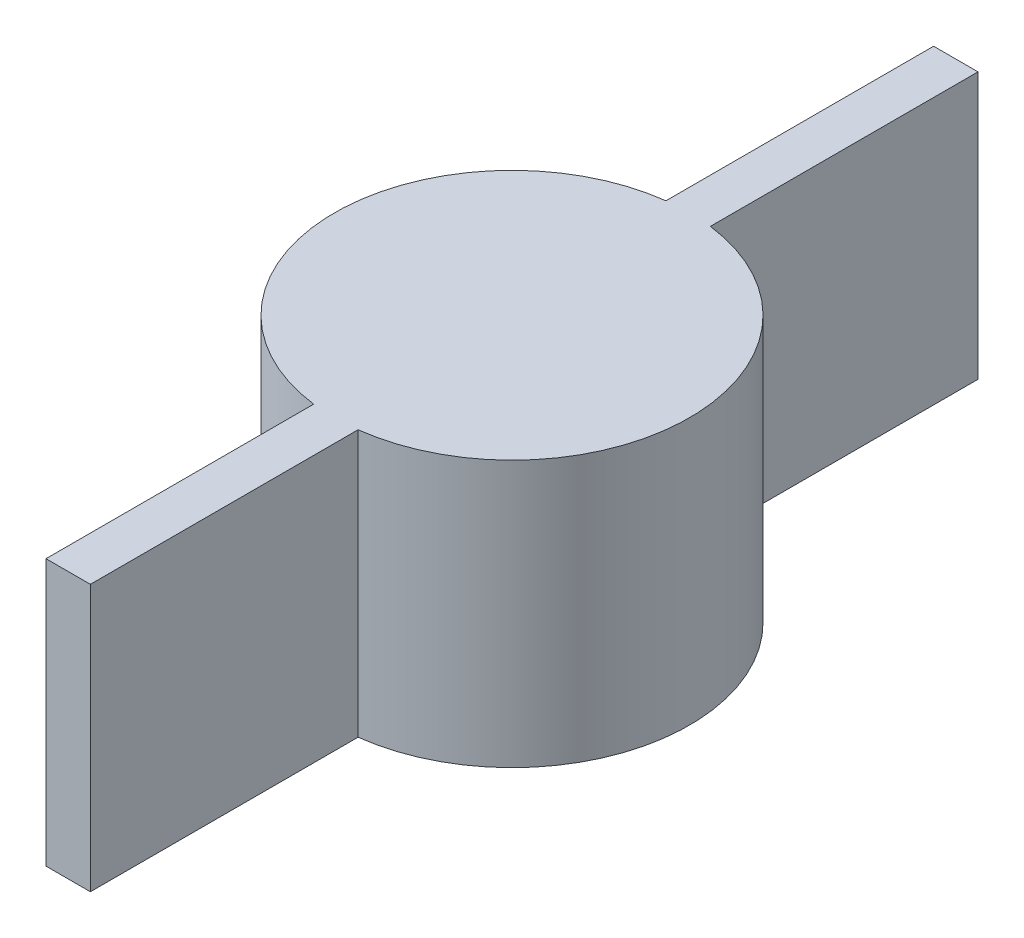
SolidWorks part; units mm, degrees
ref_plane "Front" through (0, 0, 0) normal (0, 0, 1) x (1, 0, 0)
ref_plane "Top" through (0, 0, 0) normal (0, 1, 0) x (1, 0, 0)
ref_plane "Right" through (0, 0, 0) normal (1, 0, 0) x (0, 0, -1)
sketch "草图1" plane through (0, 0, 0) normal (0, 1, 0) x (1, 0, 0)
  line L0 (0, 58.1692) -> (0, -55.7643) construction
  line L1 (-43.5893, 0) -> (40.8838, 0) construction
  line L2 (-2.5, 50) -> (-2.5, 19.8431)
  line L3 (-2.5, -50) -> (2.5, -50)
  line L4 (2.5, -50) -> (2.5, -19.8431)
  line L5 (2.5, 50) -> (-2.5, 50)
  line L6 (-2.5, -19.8431) -> (-2.5, -50)
  line L7 (2.5, 19.8431) -> (2.5, 50)
  arc A0 (-2.5, 19.8431) -> (-2.5, -19.8431) centre (0, 0) ccw
  arc A1 (2.5, -19.8431) -> (2.5, 19.8431) centre (0, 0) ccw
  dimension "D1" = 20
  dimension "D2" = 5
  dimension "D3" = 100
extrude "凸台-拉伸1" add sketch "草图1" along normal blind 30
ref_axis "转轴中心轴" through (0, 50, 0) along (0, -1, 0)
